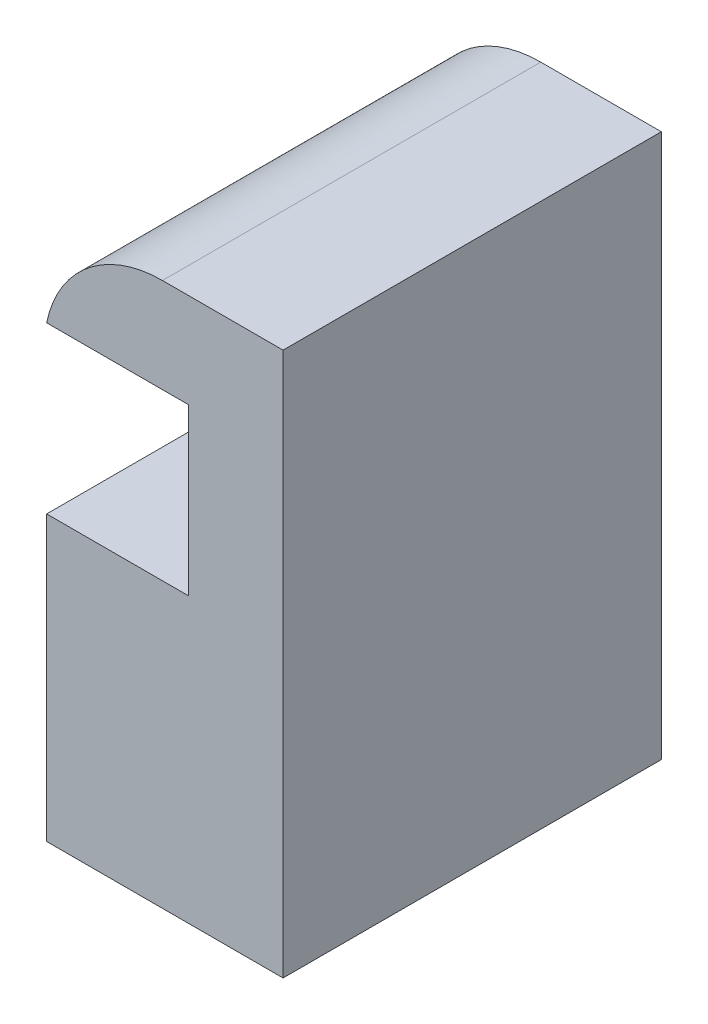
SolidWorks part; units mm, degrees
ref_plane "Front Plane" through (0, 0, 0) normal (0, 0, 1) x (1, 0, 0)
ref_plane "Top Plane" through (0, 0, 0) normal (0, 1, 0) x (1, 0, 0)
ref_plane "Right Plane" through (0, 0, 0) normal (1, 0, 0) x (0, 0, -1)
sketch "Sketch1" plane through (0, 0, 0) normal (0, 0, 1) x (1, 0, 0)
  line L0 (0, 0) -> (10, 0)
  line L1 (10, 0) -> (10, 23)
  line L2 (10, 23) -> (0, 23)
  line L9 (0, 12) -> (0, 0)
  line L10 (0, 12) -> (6, 12)
  line L11 (6, 12) -> (6, 19)
  line L12 (6, 19) -> (0, 19)
  line L13 (0, 19) -> (0, 23)
  dimension "D1" = 10
  dimension "D2" = 12
  dimension "D3" = 7
  dimension "D4" = 4
  dimension "D5" = 6
  dimension "D6" = 6
extrude "Boss-Extrude1" add sketch "Sketch1" along normal blind 16
fillet "Fillet1" radius 5 1 edges at (0, 23, 8)
